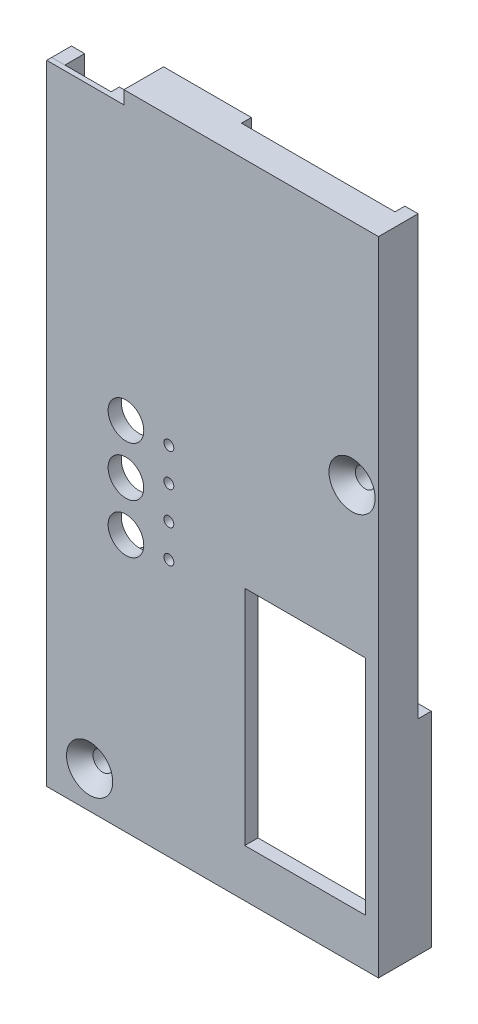
SolidWorks part; units mm, degrees
ref_plane "Front Plane" through (0, 0, 0) normal (0, 0, 1) x (1, 0, 0)
ref_plane "Top Plane" through (0, 0, 0) normal (0, 1, 0) x (1, 0, 0)
ref_plane "Right Plane" through (0, 0, 0) normal (1, 0, 0) x (0, 0, -1)
sketch "Sketch1" plane through (0, 0, 0) normal (0, 0, 1) x (1, 0, 0)
  line L1 (0, 0) -> (50.25, 0)
  line L2 (0, 0) -> (0, -97.25)
  line L3 (0, -97.25) -> (50.25, -97.25)
  line L4 (50.25, 0) -> (50.25, -97.25)
  dimension "D1" = 50.25
  dimension "D2" = 97.25
extrude "Boss-Extrude1" add sketch "Sketch1" along normal blind 2
sketch "Sketch2" plane through (0, 0, 2) normal (0, 0, 1) x (1, 0, 0)
  line L0 (0, 0) -> (0, -97.25) construction
  line L1 (30, -56.25) -> (48.25, -56.25)
  line L2 (30, -56.25) -> (30, -90)
  line L3 (30, -90) -> (48.25, -90)
  line L4 (48.25, -56.25) -> (48.25, -90)
  line L5 (0, -97.25) -> (50.25, -97.25) construction
  line L6 (12, -58.25) -> (12, -43.25) construction
  line L7 (50.25, -97.25) -> (50.25, 0) construction
  line L8 (18.5, -58.25) -> (18.5, -53.25) construction
  line L10 (18.5, -53.25) -> (18.5, -48.25) construction
  line L11 (18.5, -48.25) -> (18.5, -43.25) construction
  circle A0 centre (12, -43.25) radius 2.7
  circle A1 centre (12, -50.75) radius 2.7
  circle A2 centre (12, -58.25) radius 2.7
  circle A3 centre (46.25, -34.59) radius 1.5
  circle A4 centre (6.5, -91.65) radius 1.5
  circle A5 centre (18.5, -43.25) radius 0.75
  circle A6 centre (18.5, -48.25) radius 0.75
  circle A7 centre (18.5, -53.25) radius 0.75
  circle A8 centre (18.5, -58.25) radius 0.75
  dimension "D6" = 5.4
  dimension "D10" = 3
  dimension "D15" = 1.5
  dimension "D1" = 30
  dimension "D2" = 48.25
  dimension "D3" = 7.25
  dimension "D4" = 41
  dimension "D5" = 15
  dimension "D7" = 46.5
  dimension "D8" = 12
  dimension "D9" = 2
  dimension "D11" = 46.25
  dimension "D12" = 62.66
  dimension "D13" = 6.5
  dimension "D14" = 5.6
  dimension "D16" = 6.5
extrude "Cut-Extrude1" cut sketch "Sketch2" against normal through all
sketch "Sketch3" plane through (0, 0, 0) normal (0, 0, -1) x (-1, 0, 0)
  line L0 (-2, -95.25) -> (-2, -2)
  line L1 (-2, -2) -> (-48.25, -2)
  line L2 (-48.25, -2) -> (-48.25, -95.25)
  line L3 (-48.25, -95.25) -> (-2, -95.25)
  line L4 (0, -97.25) -> (0, 0)
  line L5 (0, 0) -> (-50.25, 0)
  line L6 (-50.25, 0) -> (-50.25, -97.25)
  line L7 (-50.25, -97.25) -> (0, -97.25)
  line L8 (0, -97.25) -> (0, 0)
  line L9 (0, 0) -> (-50.25, 0)
  line L10 (-50.25, 0) -> (-50.25, -97.25)
  line L11 (-50.25, -97.25) -> (0, -97.25)
  dimension "D1" = 0
  dimension "D2" = 2
extrude "Boss-Extrude2" add sketch "Sketch3" along normal blind 4
sketch "Sketch4" plane through (0, 0, 0) normal (0, 0, -1) x (-1, 0, 0)
  line L0 (-48.25, -2) -> (-48.25, -56.25) construction
  line L1 (-46.25, -31.59) -> (-48.25, -31.59)
  line L3 (-46.25, -37.59) -> (-48.25, -37.59)
  line L4 (-48.25, -31.59) -> (-48.25, -37.59)
  circle A1 centre (-46.25, -34.59) radius 1.5 construction
  circle A2 centre (-46.25, -34.59) radius 1.5
  arc A3 (-46.25, -37.59) -> (-46.25, -31.59) centre (-46.25, -34.59) ccw
  circle A4 centre (-6.5, -91.65) radius 3
  circle A5 centre (-6.5, -91.65) radius 1.5 construction
  circle A6 centre (-6.5, -91.65) radius 1.5
  point P15 (-45.8017, -37.5563)
  dimension "D1" = 3
extrude "Boss-Extrude3" add sketch "Sketch4" along normal blind 4
sketch "Sketch6" plane through (0, 0, -4) normal (0, 0, -1) x (-1, 0, 0)
  line L0 (0, 0) -> (-50.25, 0) construction
  line L1 (-11.7, 0) -> (0, 0)
  line L2 (-11.7, 0) -> (-11.7, -2)
  line L3 (-11.7, -2) -> (-2, -2)
  line L5 (-2, -2) -> (-48.25, -2) construction
  line L6 (-2, -95.25) -> (-2, -2) construction
  line L7 (0, -97.25) -> (-2, -97.25)
  line L8 (0, -97.25) -> (0, 0)
  line L10 (-2, -97.25) -> (-2, -2)
  point P9 (-0.0791, 0)
  dimension "D1" = 11.7
extrude "Cut-Extrude2" cut sketch "Sketch6" against normal blind 4
sketch "Sketch7" plane through (0, 0, 0) normal (0, 0, -1) x (-1, 0, 0)
  line L0 (0, 0) -> (-11.7, 0) construction
  line L1 (0, -97.25) -> (-2, -97.25)
  line L2 (0, -97.25) -> (0, 0)
  line L3 (0, 0) -> (-2, 0)
  line L4 (-2, -97.25) -> (-2, 0)
  dimension "D1" = 2
extrude "Cut-Extrude3" cut sketch "Sketch7" against normal blind 1
sketch "Sketch8" plane through (0, 0, 0) normal (0, 0, -1) x (-1, 0, 0)
  line L1 (-11.7, -2) -> (0, -2)
  line L2 (-11.7, -2) -> (-11.7, 0)
  line L3 (-11.7, 0) -> (0, 0)
  line L4 (0, -2) -> (0, 0)
extrude "Cut-Extrude4" cut sketch "Sketch8" against normal through all both and the other way through all
sketch "Sketch9" plane through (0, 0, 0) normal (0, 0, -1) x (-1, 0, 0)
  line L0 (0, -97.25) -> (0, -2) construction
  line L1 (0, -7) -> (-9, -7)
  line L2 (0, -7) -> (0, 0)
  line L3 (0, 0) -> (-9, 0)
  line L4 (-9, -7) -> (-9, 0)
  line L5 (-11.7, 0) -> (-50.25, 0) construction
  dimension "D1" = 9
  dimension "D2" = 7
extrude "Cut-Extrude5" cut sketch "Sketch9" against normal blind 1.25 and the other way through all
sketch "Sketch10" plane through (0, 0, 0) normal (0, 0, -1) x (-1, 0, 0)
  circle A0 centre (-18.5, -43.25) radius 0.75 construction
  circle A1 centre (-18.5, -43.25) radius 0.75
  circle A2 centre (-18.5, -48.25) radius 0.75 construction
  circle A3 centre (-18.5, -48.25) radius 0.75
  circle A4 centre (-18.5, -53.25) radius 0.75 construction
  circle A5 centre (-18.5, -53.25) radius 0.75
  circle A6 centre (-18.5, -58.25) radius 0.75 construction
  circle A7 centre (-18.5, -58.25) radius 0.75
  circle A8 centre (-18.5, -58.25) radius 2.25
  circle A9 centre (-18.5, -53.25) radius 2.25
  circle A10 centre (-18.5, -48.25) radius 2.25
  circle A11 centre (-18.5, -43.25) radius 2.25
  dimension "D1" = 1.5
extrude "Boss-Extrude4" add sketch "Sketch10" along normal blind 2.5
sketch "Sketch11" plane through (0, 0, -4) normal (0, 0, -1) x (-1, 0, 0)
  line L0 (-11.7, 0) -> (-50.25, 0) construction
  line L1 (-48.25, -2) -> (-25, -2)
  line L2 (-48.25, -2) -> (-48.25, 0)
  line L3 (-48.25, 0) -> (-25, 0)
  line L4 (-25, -2) -> (-25, 0)
  line L5 (0, -97.25) -> (0, -7) construction
  dimension "D1" = 25
extrude "Cut-Extrude6" cut sketch "Sketch11" against normal blind 1.5
chamfer "Chamfer1" distance 2 angle 45 2 edges at (8, -91.65, 2) (47.75, -34.59, 2)
sketch "Sketch12" plane through (0, 0, 0) normal (0, 0, -1) x (-1, 0, 0)
  line L0 (-50.25, -97.25) -> (-2, -97.25) construction
  line L1 (0, -97.25) -> (0, -7) construction
  circle A0 centre (-10, -13.25) radius 3
  circle A1 centre (-11, -33) radius 3
  circle A2 centre (-10, -67.25) radius 3
  circle A3 centre (-10, -77.25) radius 3
  circle A4 centre (-39, -44.25) radius 3
  point P10 (-31.1601, -46.4785)
  point P15 (0, 0)
  dimension "D3" = 6
  dimension "D1" = 53
  dimension "D2" = 39
  dimension "D4" = 11
  dimension "D5" = 64.25
  dimension "D6" = 10
  dimension "D7" = 20
  dimension "D8" = 30
  dimension "D9" = 10
  dimension "D10" = 84
extrude "Boss-Extrude5" add sketch "Sketch12" along normal blind 4
sketch "Sketch13" plane through (0, 0, -4) normal (0, 0, -1) x (-1, 0, 0)
  line L1 (-50.25, -97.25) -> (-46.25, -97.25)
  line L2 (-50.25, -97.25) -> (-50.25, -66.25)
  line L3 (-50.25, -66.25) -> (-46.25, -66.25)
  line L4 (-46.25, -97.25) -> (-46.25, -66.25)
  dimension "D1" = 4
  dimension "D2" = 31
extrude "Boss-Extrude6" add sketch "Sketch13" along normal blind 2
sketch "Sketch14" plane through (0, 0, 1.25) normal (0, 0, -1) x (-1, 0, 0)
  line L1 (0, -2) -> (-2, -2)
  line L2 (0, -2) -> (0, -7)
  line L3 (0, -7) -> (-2, -7)
  line L4 (-2, -2) -> (-2, -7)
  dimension "D1" = 5
  dimension "D2" = 2
extrude "Boss-Extrude9" add sketch "Sketch14" along normal blind 3 separate body
